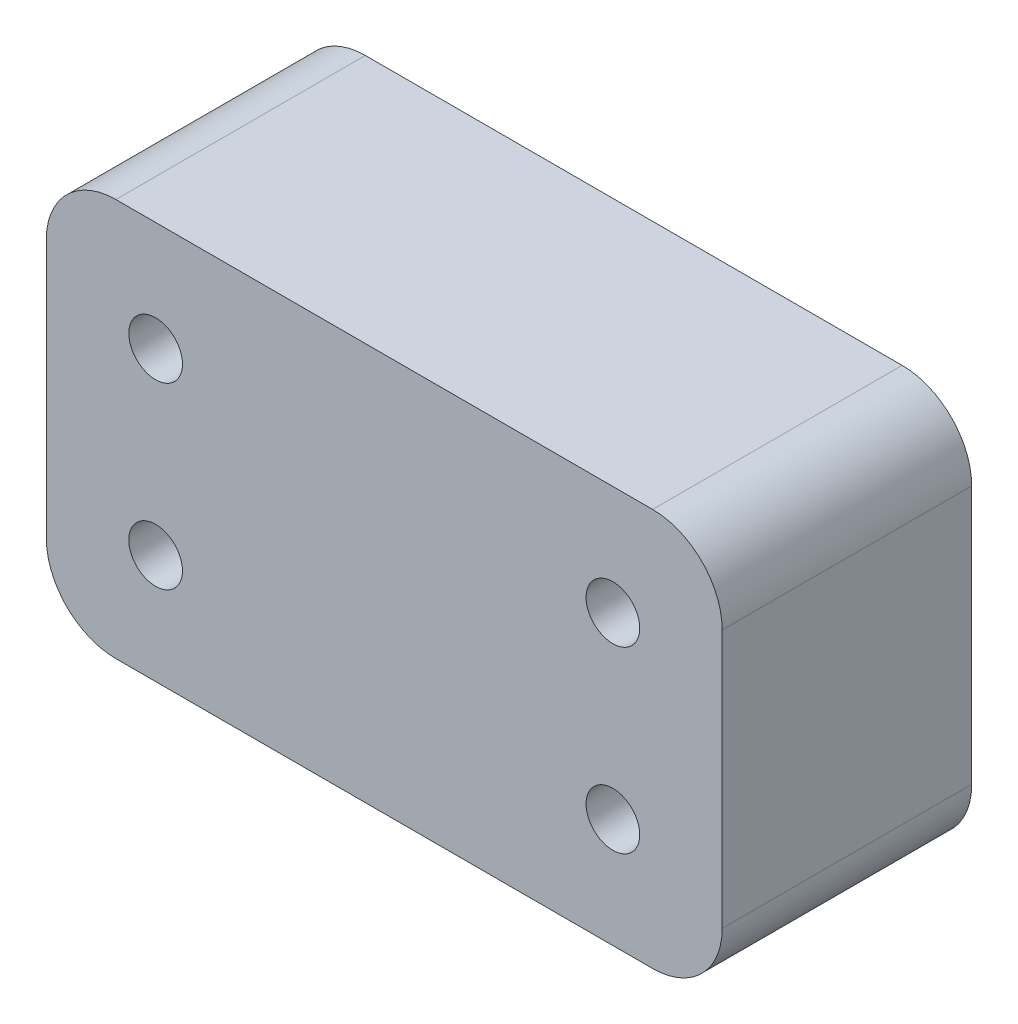
SolidWorks part; units mm, degrees
ref_plane "Front Plane" through (0, 0, 0) normal (0, 0, 1) x (1, 0, 0)
ref_plane "Top Plane" through (0, 0, 0) normal (0, 1, 0) x (1, 0, 0)
ref_plane "Right Plane" through (0, 0, 0) normal (1, 0, 0) x (0, 0, -1)
sketch "Sketch1" plane through (0, 0, 0) normal (0, 0, 1) x (1, 0, 0)
  line L0 (38.9055, 79) -> (-21.0984, 79)
  line L1 (38.9055, 79) -> (38.9055, 47)
  line L4 (-21.0945, 79) -> (-21.0945, 47)
  line L6 (38.9055, 47) -> (-21.0945, 47)
  circle A4 centre (31.9055, 72) radius 2.1 construction
  dimension "D1" = 7
  dimension "D2" = 7
extrude "Boss-Extrude1" add sketch "Sketch1" along normal blind 25.1 contours L6 L1 L0 L4 region at (8.9055, 63, 0)
hole_wizard "M5 Clearance Hole1" positions "Sketch2" profile "Sketch3" hole size "M5" standard "ISO" end condition through all
sketch "Sketch2" plane through (0, 0, 25.1) normal (0, 0, -1) x (-1, 0, 0)
  line L0 (-38.9055, 79) -> (-38.9055, 47) construction
  line L1 (-38.9055, 47) -> (21.0945, 47) construction
  point P0 (-31.9055, 72)
  point P2 (-31.9055, 54)
  point P4 (14.0945, 54)
  point P6 (14.0945, 72)
  dimension "D1" = 46
  dimension "D2" = 18
  dimension "D3" = 46
  dimension "D4" = 18
  dimension "D5" = 7
  dimension "D6" = 7
sketch "Sketch3" plane through (31.9055, 72, 25.1) normal (1, 0, 0) x (0, -1, 0)
  line L0 (0, 0) -> (0, 25.1)
  line L1 (0, 25.1) -> (2.7, 25.1)
  line L2 (2.7, 25.1) -> (2.7, 0)
  line L5 (2.7, 0) -> (0, 0)
  line L11 (0, -6.35) -> (0, 107.95) construction
  dimension "Thru Hole Dia." = 5.4
  dimension "Thru Hole Depth" = 25.1
fillet "Fillet1" radius 3 4 edges at (38.9055, 47, 12.55) (-21.0945, 47, 12.55) (38.9055, 79, 12.55) (-21.0945, 79, 12.55)
sketch "Sketch4" plane through (0, 0, 25.1) normal (0, 0, 1) x (1, 0, 0)
  line L8 (42.9055, 50) -> (42.9055, 76)
  line L9 (35.9055, 83) -> (-18.0945, 83)
  line L10 (-25.0945, 76) -> (-25.0945, 50)
  line L11 (-18.0945, 43) -> (35.9055, 43)
  line L12 (42.9055, 50) -> (42.9055, 76)
  line L13 (35.9055, 83) -> (-18.0945, 83)
  line L14 (-25.0945, 76) -> (-25.0945, 50)
  line L15 (-18.0945, 43) -> (35.9055, 43)
  line L17 (35.9055, 79) -> (-18.0945, 79)
  line L18 (38.9055, 50) -> (38.9055, 76)
  line L19 (-18.0945, 47) -> (35.9055, 47)
  line L20 (-21.0945, 76) -> (-21.0945, 50)
  line L21 (35.9055, 79) -> (-18.0945, 79)
  line L22 (38.9055, 50) -> (38.9055, 76)
  line L23 (-18.0945, 47) -> (35.9055, 47)
  line L24 (-21.0945, 76) -> (-21.0945, 50)
  arc A8 (42.9055, 76) -> (35.9055, 83) centre (35.9055, 76) ccw
  arc A9 (-18.0945, 83) -> (-25.0945, 76) centre (-18.0945, 76) ccw
  arc A10 (-25.0945, 50) -> (-18.0945, 43) centre (-18.0945, 50) ccw
  arc A11 (35.9055, 43) -> (42.9055, 50) centre (35.9055, 50) ccw
  arc A12 (42.9055, 76) -> (35.9055, 83) centre (35.9055, 76) ccw
  arc A13 (-18.0945, 83) -> (-25.0945, 76) centre (-18.0945, 76) ccw
  arc A14 (-25.0945, 50) -> (-18.0945, 43) centre (-18.0945, 50) ccw
  arc A15 (35.9055, 43) -> (42.9055, 50) centre (35.9055, 50) ccw
  arc A17 (38.9055, 76) -> (35.9055, 79) centre (35.9055, 76) ccw
  arc A18 (35.9055, 47) -> (38.9055, 50) centre (35.9055, 50) ccw
  arc A19 (-21.0945, 50) -> (-18.0945, 47) centre (-18.0945, 50) ccw
  arc A20 (-18.0945, 79) -> (-21.0945, 76) centre (-18.0945, 76) ccw
  arc A21 (38.9055, 76) -> (35.9055, 79) centre (35.9055, 76) ccw
  arc A22 (35.9055, 47) -> (38.9055, 50) centre (35.9055, 50) ccw
  arc A23 (-21.0945, 50) -> (-18.0945, 47) centre (-18.0945, 50) ccw
  arc A24 (-18.0945, 79) -> (-21.0945, 76) centre (-18.0945, 76) ccw
  dimension "D1" = 4
  dimension "D2" = 0
extrude "Boss-Extrude2" add sketch "Sketch4" against normal up to surface (25.1 mm away) up to face at (34.6055, 72, 0)
